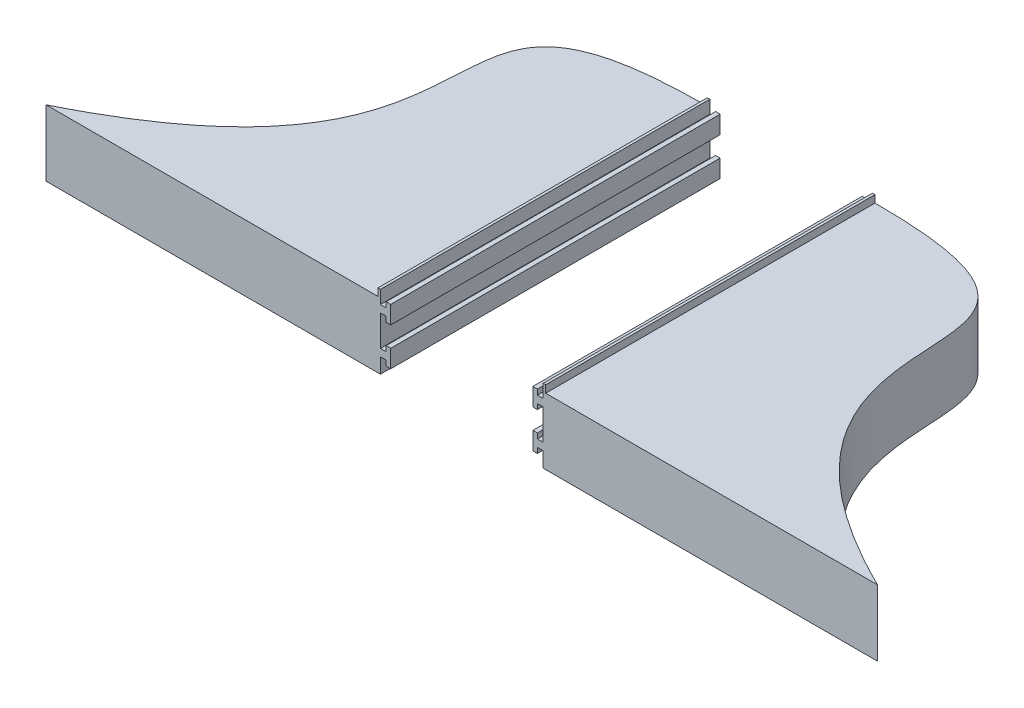
SolidWorks part; units mm, degrees
material "PLA"
ref_plane "Front Plane" through (0, 0, 0) normal (0, 0, 1) x (1, 0, 0)
ref_plane "Top Plane" through (0, 0, 0) normal (0, 1, 0) x (1, 0, 0)
ref_plane "Right Plane" through (0, 0, 0) normal (1, 0, 0) x (0, 0, -1)
ref_plane "Rail start" through (0, 0, -130) normal (0, 0, 1) x (1, 0, 0)
sketch "Sketch1" plane through (0, 0, -130) normal (0, 0, 1) x (1, 0, 0)
  line L440 (-32.1, -15.0497) -> (-32.1, -21)
  line L441 (-29.8428, -15.0497) -> (-32.1, -15.0497)
  line L442 (-29.8428, -17.1188) -> (-29.8428, -15.0497)
  line L443 (-28.0428, -17.1188) -> (-29.8428, -17.1188)
  line L444 (-28.0428, -10.1001) -> (-28.0428, -17.1188)
  line L445 (-29.8428, -10.1001) -> (-28.0428, -10.1001)
  line L446 (-29.8428, -12.1692) -> (-29.8428, -10.1001)
  line L447 (-32.1, -12.1692) -> (-29.8428, -12.1692)
  line L448 (-32.1, -0.0497) -> (-32.1, -12.1692)
  line L449 (-29.8428, -0.0497) -> (-32.1, -0.0497)
  line L450 (-29.8428, -2.1188) -> (-29.8428, -0.0497)
  line L451 (-28.0428, -2.1188) -> (-29.8428, -2.1188)
  line L452 (-28.0428, 4.8999) -> (-28.0428, -2.1188)
  line L453 (-29.8428, 4.8999) -> (-28.0428, 4.8999)
  line L454 (-29.8428, 2.8308) -> (-29.8428, 4.8999)
  line L455 (-32.1, 2.8308) -> (-29.8428, 2.8308)
  line L456 (-32.1, 7.9999) -> (-32.1, 2.8308)
  line L457 (-32.1, -15.0497) -> (-32.1, -21)
  line L458 (-29.8428, -15.0497) -> (-32.1, -15.0497)
  line L459 (-29.8428, -17.1188) -> (-29.8428, -15.0497)
  line L460 (-28.0428, -17.1188) -> (-29.8428, -17.1188)
  line L461 (-28.0428, -10.1001) -> (-28.0428, -17.1188)
  line L462 (-29.8428, -10.1001) -> (-28.0428, -10.1001)
  line L463 (-29.8428, -12.1692) -> (-29.8428, -10.1001)
  line L464 (-32.1, -12.1692) -> (-29.8428, -12.1692)
  line L465 (-32.1, -0.0497) -> (-32.1, -12.1692)
  line L466 (-29.8428, -0.0497) -> (-32.1, -0.0497)
  line L467 (-29.8428, -2.1188) -> (-29.8428, -0.0497)
  line L468 (-28.0428, -2.1188) -> (-29.8428, -2.1188)
  line L469 (-28.0428, 4.8999) -> (-28.0428, -2.1188)
  line L470 (-29.8428, 4.8999) -> (-28.0428, 4.8999)
  line L471 (-29.8428, 2.8308) -> (-29.8428, 4.8999)
  line L472 (-32.1, 2.8308) -> (-29.8428, 2.8308)
  line L473 (-32.1, 7.9999) -> (-32.1, 2.8308)
  line L474 (-32.1, -21) -> (-33.1, -21)
  line L475 (-33.1, -21) -> (-33.1, 7.9999)
  line L476 (-33.1, 7.9999) -> (-32.1, 7.9999)
  dimension "D1" = 0.1
extrude "Boss-Extrude1" add sketch "Sketch1" along normal up to surface (130 mm away)
sketch "Sketch2" plane through (75.2969, -0.8946, -218.7008) normal (0, 1, 0) x (1, 0, 0)
  line L0 (-108.3969, -88.7008) -> (-108.3969, -218.7008)
  line L2 (-239.3767, -218.7008) -> (-108.3969, -218.7008)
  line L4 (-108.3969, -218.7008) -> (-108.3969, -88.7008) construction
  line L5 (-107.3969, -218.7008) -> (-107.3969, -88.7008) construction
  line L9 (-108.3969, -88.7008) -> (-226.6247, -88.7008) construction
  line L10 (-226.6247, -88.7008) -> (-107.3969, -153.7008) construction
  line L11 (-107.3969, -153.7008) -> (-239.3767, -218.7008) construction
  line L15 (-108.3969, -218.7008) -> (-108.3969, -88.7008) construction
  spline S0 degree 3 poles (-108.3969, -88.7008) (-226.6247, -88.7008) (-107.3969, -153.7008) (-239.3767, -218.7008) knots 0 0 0 0 1 1 1 1
  point P2 (0, 0)
  point P3 (0, 0)
  point P5 (-108.3969, -167.0908)
  point P6 (-108.3969, -157.0329)
  point P9 (-108.3969, -101.9477)
  point P10 (-108.3969, -88.7008)
  point P11 (-108.3969, -167.0908)
  point P12 (-214.4004, -88.7008)
  point P13 (-167.4688, -121.0809)
  point P16 (0, 0)
  point P17 (0, 0)
  point P18 (0, 0)
  point P19 (-234.2034, -167.0908)
  point P20 (-250.9426, -167.0908)
  point P21 (-203.1964, -167.0908)
  point P22 (-239.3767, -167.0908)
  point P23 (-161.4688, -120.7682)
  point P24 (-226.6247, -88.7008)
  point P25 (-108.3969, -167.0908)
  point P26 (-108.3969, -218.7008)
  point P27 (-107.3969, -153.7008)
extrude "Boss-Extrude2" add sketch "Sketch2" along normal blind 6 and the other way up to surface (20.1054 mm away) other way up to face at (-32.6, -21, -65)
mirror "Mirror1" about plane through (0, 0, 0) normal (1, 0, 0) of bodies 102
